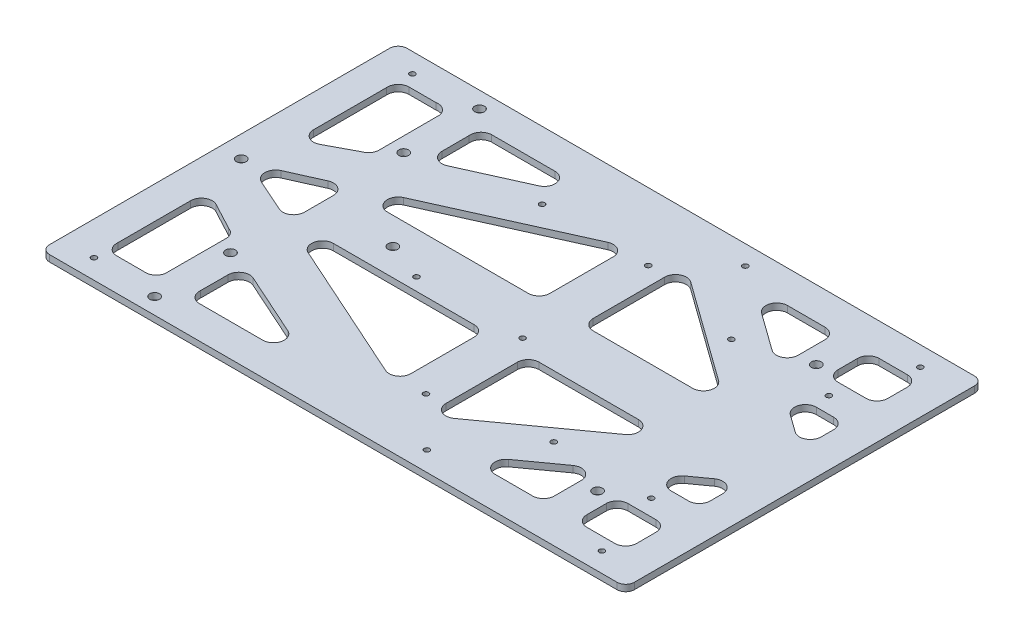
SolidWorks part; units mm, degrees
ref_plane "Alzado" through (0, 0, 0) normal (0, 0, 1) x (1, 0, 0)
ref_plane "Planta" through (0, 0, 0) normal (0, 1, 0) x (1, 0, 0)
ref_plane "Vista lateral" through (0, 0, 0) normal (1, 0, 0) x (0, 0, -1)
sketch "Croquis1" plane through (0, 0, 0) normal (0, 1, 0) x (1, 0, 0)
  line L1 (135, -82.5) -> (-135, -82.5)
  line L2 (135, -82.5) -> (135, 82.5)
  line L3 (135, 82.5) -> (-135, 82.5)
  line L4 (-135, -82.5) -> (-135, 82.5)
  line L5 (135, -82.5) -> (-135, 82.5) construction
  line L6 (135, 82.5) -> (-135, -82.5) construction
  point P0 (0, 0)
  dimension "D1" = 165
  dimension "D2" = 270
extrude "Saliente-Extruir1" add sketch "Croquis1" along normal blind 3
fillet "Redondeo1" radius 4 4 edges at (-135, 1.5, -82.5) (135, 1.5, -82.5) (135, 1.5, 82.5) (-135, 1.5, 82.5)
sketch "Croquis2" plane through (0, 3, 0) normal (0, 1, 0) x (1, 0, 0)
  line L0 (131, 82.5) -> (-131, 82.5) construction
  line L1 (135, -78.5) -> (135, 78.5) construction
  circle A0 centre (90, 50.5) radius 2.25
  dimension "D1" = 4.5
  dimension "D2" = 32
  dimension "D3" = 45
extrude "Cortar-Extruir1" cut sketch "Croquis2" against normal through all
mirror "Simetría1" about plane through (0, 0, 0) normal (0, 0, 1) of "Cortar-Extruir1"
sketch "Croquis3" plane through (0, 3, 0) normal (0, 1, 0) x (1, 0, 0)
  line L0 (-135, 78.5) -> (-135, -78.5) construction
  line L1 (131, 82.5) -> (-131, 82.5) construction
  line L2 (-135, 0) -> (-113.8944, 0) construction
  circle A0 centre (-90, 75) radius 2.25
  circle A1 centre (-90, -75) radius 2.25
  dimension "D1" = 4.5
  dimension "D2" = 45
  dimension "D3" = 7.5
extrude "Cortar-Extruir2" cut sketch "Croquis3" against normal through all
sketch "Croquis4" plane through (0, 3, 0) normal (0, 1, 0) x (1, 0, 0)
  line L0 (0, 82.5) -> (0, -82.5) construction
  line L1 (131, 82.5) -> (-131, 82.5) construction
  line L2 (-131, -82.5) -> (131, -82.5) construction
  line L3 (-135, 0) -> (135, 0) construction
  line L4 (-135, 78.5) -> (-135, -78.5) construction
  line L5 (135, -78.5) -> (135, 78.5) construction
  line L6 (0, -82.5) -> (131, -82.5) construction
  line L7 (135, -82.5) -> (135, 78.5) construction
  line L8 (131, 82.5) -> (0, 82.5) construction
  line L9 (115, 67.5) -> (102.5, 67.5)
  line L12 (110.2817, 0) -> (2.6409, -64.5845) construction
  line L13 (131, 67.5) -> (-131, 67.5) construction
  line L14 (4.9275, 63.2125) -> (110.2817, 0) construction
  line L15 (15, 10) -> (75.5635, 10)
  line L16 (131, 82.5) -> (-131, 82.5) construction
  line L17 (15, -10) -> (75.5635, -10)
  line L18 (10, 51.3381) -> (10, 15)
  line L19 (17.5725, 55.6256) -> (78.136, 19.2875)
  line L20 (78.136, -19.2875) -> (17.5725, -55.6256)
  line L24 (52.1339, 58.2125) -> (74.9275, 44.5363)
  line L29 (15.2174, 80.3624) -> (149.1548, 0) construction
  line L30 (90, 50.5) -> (90, 67.5) construction
  line L31 (149.1548, 0) -> (12.9308, -81.7344) construction
  line L32 (99.9275, 29.5363) -> (112.4275, 22.0363)
  line L34 (82.5, 62.5) -> (82.5, 48.8238)
  line L36 (97.5, 62.5) -> (97.5, 33.8238)
  line L37 (120, 26.3238) -> (120, 62.5)
  line L38 (77.5, 67.5) -> (54.7063, 67.5)
  line L39 (10, -15) -> (10, -51.3381)
  arc A3 (120, 62.5) -> (115, 67.5) centre (115, 62.5) ccw
  arc A4 (120, 26.3238) -> (112.4275, 22.0363) centre (115, 26.3238) cw
  arc A5 (99.9275, 29.5363) -> (97.5, 33.8238) centre (102.5, 33.8238) cw
  arc A6 (102.5, 67.5) -> (97.5, 62.5) centre (102.5, 62.5) ccw
  arc A7 (10, -51.3381) -> (17.5725, -55.6256) centre (15, -51.3381) ccw
  arc A9 (10, 51.3381) -> (17.5725, 55.6256) centre (15, 51.3381) cw
  arc A10 (75.5635, 10) -> (78.136, 19.2875) centre (75.5635, 15) ccw
  arc A11 (75.5635, -10) -> (78.136, -19.2875) centre (75.5635, -15) cw
  arc A12 (15, 10) -> (10, 15) centre (15, 15) cw
  arc A13 (15, -10) -> (10, -15) centre (15, -15) ccw
  arc A14 (82.5, 48.8238) -> (74.9275, 44.5363) centre (77.5, 48.8238) cw
  arc A15 (77.5, 67.5) -> (82.5, 62.5) centre (77.5, 62.5) cw
  arc A16 (52.1339, 58.2125) -> (54.7063, 67.5) centre (54.7063, 62.5) cw
  point P44 (97.5, 30.9929)
  point P64 (10, -10)
  dimension "D5" = 33.6762
  dimension "D6" = 5
  dimension "D7" = 5
  dimension "D13" = 5
  dimension "D14" = 5
  dimension "D15" = 5
  dimension "D16" = 22.0363
  dimension "D2" = 5
  dimension "D4" = 15
  dimension "D8" = 15
  dimension "D10" = 10
  dimension "D11" = 10
  dimension "D12" = 10
  dimension "D3" = 20
  dimension "D1" = 15
extrude "Cortar-Extruir3" [suppressed] cut sketch "Croquis4" against normal through all
mirror "Simetría4" [suppressed] about plane through (0, 0, 0) normal (1, 0, 0)
sketch "Croquis5" plane through (0, 3, 0) normal (0, 1, 0) x (1, 0, 0)
  line L0 (135, -78.5) -> (135, 78.5) construction
  line L1 (-131, -82.5) -> (131, -82.5) construction
  line L2 (131, 82.5) -> (-131, 82.5) construction
  circle A0 centre (-119.5, 73.5) radius 1.75
  circle A1 centre (34.2, 73.5) radius 1.75
  circle A2 centre (115, 73.5) radius 1.75
  circle A3 centre (115, -73.5) radius 1.75
  circle A4 centre (34.2, -73.5) radius 1.75
  circle A5 centre (-119.5, -73.5) radius 1.75
  point P0 (-119.5, 73.5)
  point P3 (34.2, 73.5)
  point P6 (115, 73.5)
  point P9 (115, -73.5)
  point P12 (34.2, -73.5)
  point P15 (-119.5, -73.5)
  dimension "D1" = 20
  dimension "D2" = 80.8
  dimension "D3" = 153.7
  dimension "D4" = 9
  dimension "D5" = 9
hole_wizard "Taladro roscado M31" positions "Croquis5" profile "Croquis6" tap size "M3" standard "ISO"
sketch "Croquis6" plane through (-119.5, 3, -73.5) normal (1, 0, 0) x (0, 0, 1)
  line L0 (0, 0) -> (0, 9.2511)
  line L1 (0, 9.2511) -> (1.25, 8.5)
  line L2 (1.25, 8.5) -> (1.25, 0)
  line L5 (1.25, 0) -> (0, 0)
  line L10 (0, 9.2511) -> (-1.25, 8.5) construction
  line L11 (0, -6.35) -> (0, 107.95) construction
  dimension "Diámetro de perforador para roscar" = 2.5
  dimension "Profundidad de perforador para roscar" = 8.5
  dimension "Ángulo de perforador" = 118
cosmetic thread "Rosca de taladro1" parameters "D1"=6, "D2"=3
cosmetic thread "Rosca de taladro2" parameters "D1"=6, "D2"=3
cosmetic thread "Rosca de taladro3" parameters "D1"=6, "D2"=3
cosmetic thread "Rosca de taladro4" parameters "D1"=6, "D2"=3
cosmetic thread "Rosca de taladro5" parameters "D1"=6, "D2"=3
cosmetic thread "Rosca de taladro6" parameters "D1"=6, "D2"=3
mirror "Simetría5" [suppressed] about plane through (0, 0, 0) normal (0, 0, 1)
mirror "Simetría7" [suppressed] about plane through (0, 0, 0) normal (1, 0, 0)
mirror "Simetría8" [suppressed] about plane through (0, 0, 0) normal (1, 0, 0)
sketch "Croquis9" plane through (0, 3, 0) normal (0, 1, 0) x (1, 0, 0)
  line L0 (-131, -82.5) -> (131, -82.5) construction
  line L2 (-135, 78.5) -> (-135, -78.5) construction
  line L4 (131, 82.5) -> (-131, 82.5) construction
  circle A0 centre (-125, 0) radius 2.25
  circle A1 centre (-90, 40) radius 2.25
  circle A2 centre (-55, 0) radius 2.25
  circle A3 centre (-90, -40) radius 2.25
  point P1 (-90, -40)
  point P3 (-55, 0)
  point P20 (0, 0)
  point P22 (0, 0)
  point P23 (0, 0)
  point P26 (0, 0)
  dimension "D1" = 4.5
  dimension "D5" = 10
  dimension "D3" = 82.5
  dimension "D6" = 45
  dimension "D2" = 42.5
  dimension "D4" = 80
  dimension "D7" = 42.5
extrude "Cortar-Extruir4" cut sketch "Croquis9" against normal blind 4
sketch "Croquis10" plane through (0, 3, 0) normal (0, 1, 0) x (1, 0, 0)
  circle A0 centre (0, 0) radius 2
  circle A1 centre (0, 60.1959) radius 2
  circle A2 centre (0, -65.3126) radius 2
  dimension "D1" = 4
extrude "Cortar-Extruir5" [suppressed] cut sketch "Croquis10" against normal through all
sketch "Croquis11" plane through (0, 3, 0) normal (0, 1, 0) x (1, 0, 0)
  point P0 (-37.4183, 51.3035)
  point P1 (11.5817, 51.3035)
  point P3 (11.5817, -6.6965)
  point P5 (-37.4183, -6.6965)
  point P7 (60.2712, 41)
  point P9 (105.2712, 41)
  point P11 (105.2712, -41)
  point P13 (60.2712, -41)
  point P17 (-37.4183, 51.3035)
  point P19 (-37.4183, -6.6965)
  point P21 (11.5817, -6.6965)
  point P23 (11.5817, 51.3035)
  point P25 (60.2712, 41)
  point P27 (60.2712, -41)
  point P29 (105.2712, -41)
  point P31 (105.2712, 41)
hole_wizard "Taladro roscado M33" positions "Croquis11" profile "Croquis13" tap size "M3" standard "ISO"
sketch "Croquis13" plane through (-37.4183, 3, -51.3035) normal (1, 0, 0) x (0, 0, 1)
  line L0 (0, 0) -> (0, 9.2511)
  line L1 (0, 9.2511) -> (1.25, 8.5)
  line L2 (1.25, 8.5) -> (1.25, 0)
  line L5 (1.25, 0) -> (0, 0)
  line L10 (0, 9.2511) -> (-1.25, 8.5) construction
  line L11 (0, -6.35) -> (0, 107.95) construction
  dimension "Diámetro de perforador para roscar" = 2.5
  dimension "Profundidad de perforador para roscar" = 8.5
  dimension "Ángulo de perforador" = 118
cosmetic thread "Rosca de taladro23" parameters "D1"=6, "D2"=3
cosmetic thread "Rosca de taladro24" parameters "D1"=6, "D2"=3
cosmetic thread "Rosca de taladro25" parameters "D1"=6, "D2"=3
cosmetic thread "Rosca de taladro26" parameters "D1"=6, "D2"=3
cosmetic thread "Rosca de taladro27" parameters "D1"=6, "D2"=3
cosmetic thread "Rosca de taladro28" parameters "D1"=6, "D2"=3
cosmetic thread "Rosca de taladro29" parameters "D1"=6, "D2"=3
cosmetic thread "Rosca de taladro30" parameters "D1"=6, "D2"=3
cosmetic thread "Rosca de taladro31" parameters "D1"=6, "D2"=3
cosmetic thread "Rosca de taladro32" parameters "D1"=6, "D2"=3
cosmetic thread "Rosca de taladro33" parameters "D1"=6, "D2"=3
cosmetic thread "Rosca de taladro34" parameters "D1"=6, "D2"=3
cosmetic thread "Rosca de taladro35" parameters "D1"=6, "D2"=3
cosmetic thread "Rosca de taladro36" parameters "D1"=6, "D2"=3
cosmetic thread "Rosca de taladro37" parameters "D1"=6, "D2"=3
cosmetic thread "Rosca de taladro38" parameters "D1"=6, "D2"=3
sketch "Croquis14" plane through (0, 3, 0) normal (0, 1, 0) x (1, 0, 0)
  line L0 (-135, 0) -> (135, 0) construction
  line L1 (-135, 78.5) -> (-135, -78.5) construction
  line L2 (135, -78.5) -> (135, 78.5) construction
  line L3 (0, 82.5) -> (0, -82.5) construction
  line L5 (-131, -82.5) -> (131, -82.5) construction
  line L6 (-120, 28.3988) -> (-120, 62.0179)
  line L7 (-100.1523, 30.6318) -> (-112.6523, 23.9842)
  line L8 (-96.7551, 61.9356) -> (-96.7099, 34.9641)
  line L9 (131, 67.5) -> (-131, 67.5)
  line L10 (120, 67.5) -> (-120, 67.5) construction
  line L11 (-115, 67.5) -> (-102.5, 67.5)
  line L12 (-120, 78.5) -> (-120, -78.5)
  line L13 (-120, 67.5) -> (-120, -67.5) construction
  line L14 (-77.0591, 67.5) -> (-47.6094, 67.5)
  line L15 (-131, -67.5) -> (131, -67.5)
  line L16 (-120, -67.5) -> (120, -67.5) construction
  line L18 (120, -78.5) -> (120, 78.5)
  line L19 (120, -67.5) -> (120, 33.5) construction
  line L25 (115, 67.5) -> (102.0282, 67.5)
  line L31 (-81.7551, 61.9607) -> (-81.734, 49.3949)
  line L32 (-45.5588, 57.9398) -> (-74.6834, 44.8431)
  line L33 (0, 46.7292) -> (0, 17.5)
  line L35 (-5, 12.5) -> (-70, 12.5)
  line L36 (25, 12.5) -> (70.8944, 12.5)
  line L37 (20, 50.52) -> (20, 17.5)
  line L38 (27.9201, 54.5787) -> (73.8145, 21.5587)
  line L39 (56.7965, 58.4413) -> (74.1081, 45.986)
  line L40 (90, 50.5) -> (90, 67.5) construction
  line L41 (104.053, 24.4413) -> (112.0799, 18.6662)
  line L42 (82.0282, 62.5) -> (82.0282, 50.0447)
  line L43 (97.0282, 62.5) -> (97.0282, 53.5)
  line L44 (120, 22.7248) -> (120, 28.5)
  line L45 (77.0282, 67.5) -> (59.7166, 67.5)
  line L48 (77.0282, -67.5) -> (59.7166, -67.5)
  line L49 (82.0282, -62.5) -> (82.0282, -50.0447)
  line L50 (56.7965, -58.4413) -> (74.1081, -45.986)
  line L51 (20, -50.52) -> (20, -17.5)
  line L52 (27.9201, -54.5787) -> (73.8145, -21.5587)
  line L53 (25, -12.5) -> (70.8944, -12.5)
  line L54 (-5, -12.5) -> (-70, -12.5)
  line L56 (0, -46.7292) -> (0, -17.5)
  line L57 (-45.5588, -57.9398) -> (-74.6834, -44.8431)
  line L58 (-81.7551, -61.9607) -> (-81.734, -49.3949)
  line L59 (-77.0591, -67.5) -> (-47.6094, -67.5)
  line L60 (-120, -28.3988) -> (-120, -62.0179)
  line L61 (-100.1523, -30.6318) -> (-112.6523, -23.9842)
  line L62 (-96.7551, -61.9356) -> (-96.7099, -34.9641)
  line L63 (-115, -67.5) -> (-102.5, -67.5)
  line L64 (102.0282, 48.5) -> (115, 48.5)
  line L65 (106.9731, 33.5) -> (115, 33.5)
  line L67 (120, 53.5) -> (120, 62.5)
  line L68 (120, 48.5) -> (120, 67.5) construction
  line L69 (120, -53.5) -> (120, -62.5)
  line L70 (102.0282, -48.5) -> (115, -48.5)
  line L71 (97.0282, -62.5) -> (97.0282, -53.5)
  line L72 (115, -67.5) -> (102.0282, -67.5)
  line L73 (106.9731, -33.5) -> (115, -33.5)
  line L74 (120, -22.7248) -> (120, -28.5)
  line L75 (104.053, -24.4413) -> (112.0799, -18.6662)
  line L76 (-7.0506, 51.2894) -> (-72.043, 22.0636)
  line L77 (-7.0506, -51.2894) -> (-72.043, -22.0636)
  arc A10 (-120, 62.0179) -> (-115, 67.5) centre (-115.0233, 62.5001) cw
  arc A11 (-120, 28.3988) -> (-112.6523, 23.9842) centre (-115, 28.3988) ccw
  arc A12 (-100.1523, 30.6318) -> (-96.7099, 34.9641) centre (-101.6918, 35.3889) ccw
  arc A13 (-102.5, 67.5) -> (-96.7551, 61.9356) centre (-101.7157, 62.5619) cw
  arc A14 (-45.5588, 57.9398) -> (-47.6094, 67.5) centre (-47.6094, 62.5) ccw
  arc A15 (-77.0591, 67.5) -> (-81.7551, 61.9607) centre (-76.7851, 62.5075) ccw
  arc A16 (-81.734, 49.3949) -> (-74.6834, 44.8431) centre (-76.734, 49.4032) ccw
  arc A17 (-5, 12.5) -> (0, 17.5) centre (-5, 17.5) ccw
  arc A18 (0, 46.7292) -> (-7.0506, 51.2894) centre (-5, 46.7292) ccw
  arc A19 (-70, 12.5) -> (-72.043, 22.0636) centre (-70, 17.5) cw
  arc A20 (120, 62.5) -> (115, 67.5) centre (115, 62.5) ccw
  arc A21 (120, 22.7248) -> (112.0799, 18.6662) centre (115, 22.7248) cw
  arc A23 (102.0282, 67.5) -> (97.0282, 62.5) centre (102.0282, 62.5) ccw
  arc A24 (20, 50.52) -> (27.9201, 54.5787) centre (25, 50.52) cw
  arc A25 (70.8944, 12.5) -> (73.8145, 21.5587) centre (70.8944, 17.5) ccw
  arc A26 (25, 12.5) -> (20, 17.5) centre (25, 17.5) cw
  arc A27 (82.0282, 50.0447) -> (74.1081, 45.986) centre (77.0282, 50.0447) cw
  arc A28 (77.0282, 67.5) -> (82.0282, 62.5) centre (77.0282, 62.5) cw
  arc A29 (56.7965, 58.4413) -> (59.7166, 67.5) centre (59.7166, 62.5) cw
  arc A34 (56.7965, -58.4413) -> (59.7166, -67.5) centre (59.7166, -62.5) ccw
  arc A35 (77.0282, -67.5) -> (82.0282, -62.5) centre (77.0282, -62.5) ccw
  arc A36 (82.0282, -50.0447) -> (74.1081, -45.986) centre (77.0282, -50.0447) ccw
  arc A37 (25, -12.5) -> (20, -17.5) centre (25, -17.5) ccw
  arc A38 (20, -50.52) -> (27.9201, -54.5787) centre (25, -50.52) ccw
  arc A39 (70.8944, -12.5) -> (73.8145, -21.5587) centre (70.8944, -17.5) cw
  arc A40 (-70, -12.5) -> (-72.043, -22.0636) centre (-70, -17.5) ccw
  arc A41 (0, -46.7292) -> (-7.0506, -51.2894) centre (-5, -46.7292) cw
  arc A42 (-5, -12.5) -> (0, -17.5) centre (-5, -17.5) cw
  arc A43 (-81.734, -49.3949) -> (-74.6834, -44.8431) centre (-76.734, -49.4032) cw
  arc A44 (-77.0591, -67.5) -> (-81.7551, -61.9607) centre (-76.7851, -62.5075) cw
  arc A45 (-45.5588, -57.9398) -> (-47.6094, -67.5) centre (-47.6094, -62.5) cw
  arc A46 (-120, -28.3988) -> (-112.6523, -23.9842) centre (-115, -28.3988) cw
  arc A47 (-100.1523, -30.6318) -> (-96.7099, -34.9641) centre (-101.6918, -35.3889) cw
  arc A48 (-102.5, -67.5) -> (-96.7551, -61.9356) centre (-101.7157, -62.5619) ccw
  arc A49 (-120, -62.0179) -> (-115, -67.5) centre (-115.0233, -62.5001) ccw
  circle A50 centre (105.2712, 41) radius 1.25 construction
  arc A51 (115, 48.5) -> (120, 53.5) centre (115, 53.5) ccw
  arc A52 (102.0282, 48.5) -> (97.0282, 53.5) centre (102.0282, 53.5) cw
  arc A53 (115, 33.5) -> (120, 28.5) centre (115, 28.5) cw
  arc A54 (104.053, 24.4413) -> (106.9731, 33.5) centre (106.9731, 28.5) cw
  arc A55 (115, -48.5) -> (120, -53.5) centre (115, -53.5) cw
  arc A56 (102.0282, -48.5) -> (97.0282, -53.5) centre (102.0282, -53.5) ccw
  arc A57 (102.0282, -67.5) -> (97.0282, -62.5) centre (102.0282, -62.5) cw
  arc A58 (120, -62.5) -> (115, -67.5) centre (115, -62.5) cw
  arc A59 (115, -33.5) -> (120, -28.5) centre (115, -28.5) ccw
  arc A60 (120, -22.7248) -> (112.0799, -18.6662) centre (115, -22.7248) ccw
  arc A61 (104.053, -24.4413) -> (106.9731, -33.5) centre (106.9731, -28.5) ccw
  point P37 (0, 0)
  point P45 (0, 0)
  point P161 (91.4624, 33.5)
  dimension "D6" = 5
  dimension "D7" = 5
  dimension "D8" = 5
  dimension "D9" = 5
  dimension "D11" = 5
  dimension "D22" = 7.5
  dimension "D23" = 7.5
  dimension "D24" = 5
  dimension "D25" = 5
  dimension "D26" = 5
  dimension "D13" = 5
  dimension "D27" = 5
  dimension "D18" = 5
  dimension "D28" = 5
  dimension "D5" = 15
  dimension "D10" = 20
  dimension "D12" = 20
  dimension "D14" = 0
  dimension "D15" = 33.02
  dimension "D16" = 39.7752
  dimension "D17" = 12.5
  dimension "D19" = 12.5
  dimension "D21" = 65
  dimension "D1" = 15
  dimension "D2" = 15
  dimension "D3" = 15
  dimension "D4" = 15
extrude "Cortar-Extruir6" cut sketch "Croquis14" against normal through all
mirror "Simetría9" about plane through (0, 0, 0) normal (0, 0, 1) of face at (11.5817, 3, -50.0535)
cosmetic thread "Rosca de taladro39" parameters "D1"=6, "D2"=3
cosmetic thread "Rosca de taladro40" parameters "D1"=6, "D2"=3
sketch "Croquis15" plane through (0, 3, 0) normal (0, 1, 0) x (1, 0, 0)
  line L0 (0, 0) -> (-135, 0) construction
  line L1 (-135, 78.5) -> (-135, -78.5) construction
  line L2 (0, 0) -> (135, 0) construction
  line L3 (-111.1343, -4.5636) -> (-96.167, -11.264)
  line L4 (-81.734, 49.3949) -> (-81.734, -49.3949) construction
  line L5 (-89.124, 6.7004) -> (-89.124, -6.7004)
  line L6 (-89.124, 49.3949) -> (-89.124, -49.3949) construction
  line L7 (-96.167, 11.264) -> (-111.1343, 4.5636)
  line L11 (135, -78.5) -> (135, 78.5) construction
  arc A1 (-96.167, -11.264) -> (-89.124, -6.7004) centre (-94.124, -6.7004) ccw
  arc A2 (-89.124, 6.7004) -> (-96.167, 11.264) centre (-94.124, 6.7004) ccw
  arc A3 (-111.1343, 4.5636) -> (-111.1343, -4.5636) centre (-109.0914, 0) ccw
  point P22 (-121.3284, 0)
  dimension "D2" = 5
  dimension "D1" = 7.39
extrude "Cortar-Extruir7" cut sketch "Croquis15" against normal through all
